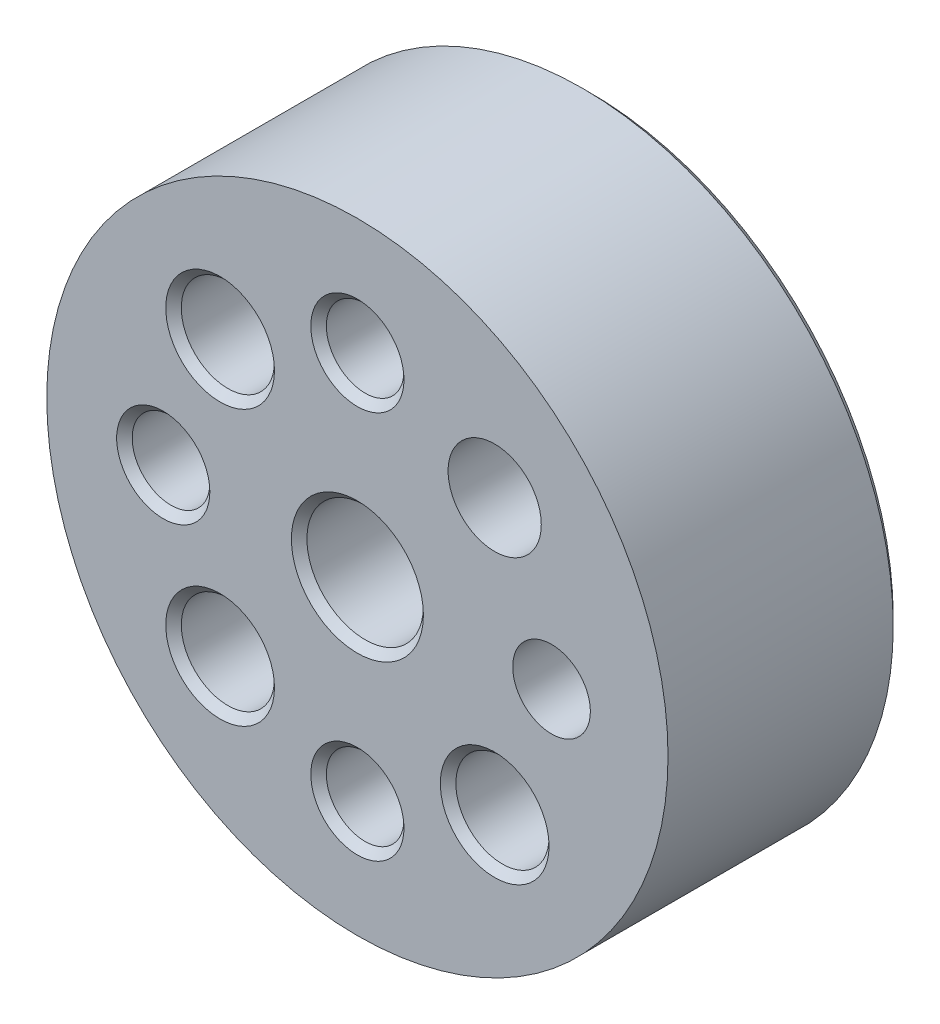
SolidWorks part; units mm, degrees
ref_plane "Ebene vorne" through (0, 0, 0) normal (0, 0, 1) x (1, 0, 0)
ref_plane "Ebene oben" through (0, 0, 0) normal (0, 1, 0) x (1, 0, 0)
ref_plane "Ebene rechts" through (0, 0, 0) normal (1, 0, 0) x (0, 0, -1)
sketch "Skizze1" plane through (0, 0, 0) normal (0, 0, 1) x (1, 0, 0)
  circle A0 centre (0, 0) radius 40
  dimension "D1" = 80
extrude "Aufsatz-Linear austragen1" add sketch "Skizze1" along normal blind 30
sketch "Skizze2" plane through (0, 0, 30) normal (0, 0, 1) x (1, 0, 0)
  line L0 (0, 40) -> (0, -40) construction
  line L1 (-40, 0) -> (40, 0) construction
  circle A0 centre (0, 0) radius 40 construction
  circle A1 centre (25, 0) radius 5
  circle A2 centre (0, -25) radius 5
  circle A3 centre (-25, 0) radius 5
  circle A4 centre (0, 25) radius 5
  point P18 (0, 0)
  dimension "D2" = 10
  dimension "D1" = 25
  dimension "D3" = 4
extrude "Schnitt-Linear austragen1" cut sketch "Skizze2" against normal blind 25
sketch "Skizze4" plane through (0, 0, 30) normal (0, 0, 1) x (1, 0, 0)
  line L0 (0, 0) -> (36.9528, 0) construction
  line L1 (0, 0) -> (17.6777, 17.6777) construction
  circle A0 centre (17.6777, 17.6777) radius 6
  circle A1 centre (17.6777, -17.6777) radius 6
  circle A2 centre (-17.6777, -17.6777) radius 6
  circle A3 centre (-17.6777, 17.6777) radius 6
  point P13 (0, 0)
  dimension "D2" = 12
  dimension "D1" = 25
  dimension "D3" = 45
  dimension "D4" = 4
extrude "Schnitt-Linear austragen5" cut sketch "Skizze4" against normal blind 25
sketch "Skizze5" plane through (0, 0, 30) normal (0, 0, 1) x (1, 0, 0)
  circle A0 centre (0, 0) radius 7.5
  dimension "D1" = 15
extrude "Schnitt-Linear austragen6" cut sketch "Skizze5" against normal blind 25
chamfer "Fase1" distance 1 angle 45 10 edges at (40, 0, 0) (7.5, 0, 30) (-20, 0, 30) (-11.6777, -17.6777, 30) (5, -25, 30) (23.6777, -17.6777, 30) (30, 0, 5) (23.6777, 17.6777, 5) (5, 25, 30) (-11.6777, 17.6777, 30)
